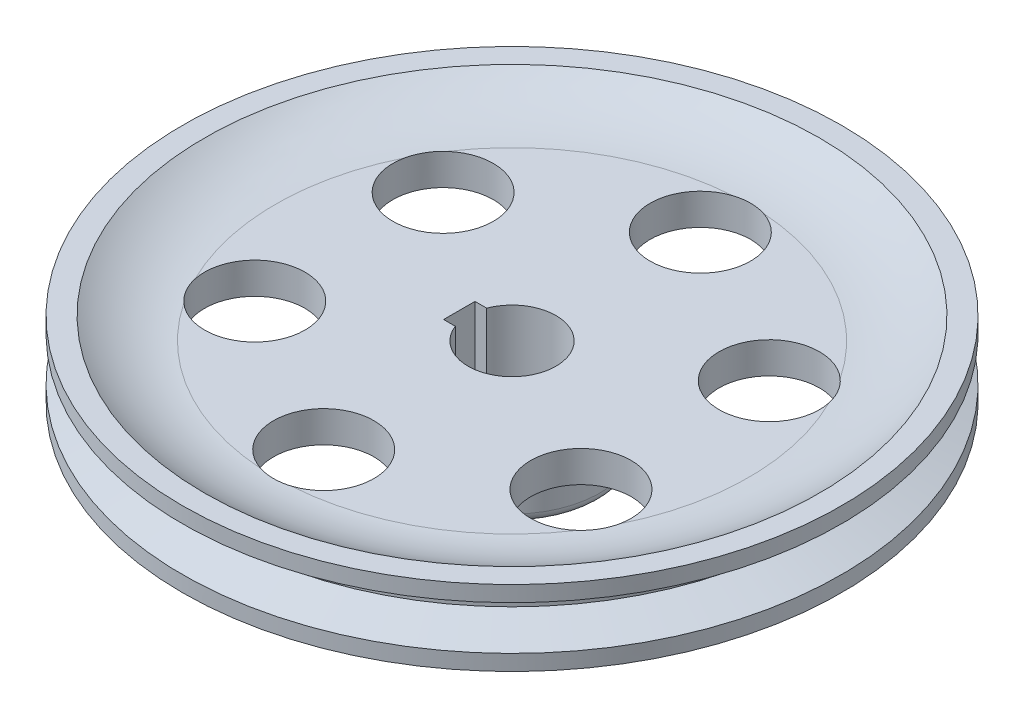
SolidWorks part; units mm, degrees
ref_plane "Front Plane" through (0, 0, 0) normal (0, 0, 1) x (1, 0, 0)
ref_plane "Top Plane" through (0, 0, 0) normal (0, 1, 0) x (1, 0, 0)
ref_plane "Right Plane" through (0, 0, 0) normal (1, 0, 0) x (0, 0, -1)
sketch "Sketch1" plane through (0, 0, 0) normal (0, 1, 0) x (1, 0, 0)
  circle A0 centre (0, 0) radius 52.5
  circle A1 centre (0, 0) radius 30 construction
  circle A2 centre (0, 30) radius 8
  circle A3 centre (25.9808, 15) radius 8
  circle A4 centre (25.9808, -15) radius 8
  circle A5 centre (0, -30) radius 8
  circle A6 centre (-25.9808, -15) radius 8
  circle A7 centre (-25.9808, 15) radius 8
  dimension "D1" = 105
  dimension "D2" = 60
  dimension "D3" = 16
  dimension "D4" = 6
extrude "Boss-Extrude1" add sketch "Sketch1" along normal mid plane 12
sketch "Sketch2" plane through (0, -6, 0) normal (0, -1, 0) x (1, 0, 0)
  circle A0 centre (0, 0) radius 14
  dimension "D1" = 28
extrude "Boss-Extrude2" add sketch "Sketch2" along normal blind 7
sketch "Sketch3" plane through (0, -13, 0) normal (0, -1, 0) x (1, 0, 0)
  line L0 (-67.4815, 0) -> (77.6813, 0) construction
  line L1 (0, 57.1338) -> (0, -59.499) construction
  line L2 (-8.4, 2.5) -> (-8.4, -2.5)
  line L3 (-8.4, 2.5) -> (-6.5383, 2.5)
  line L4 (-8.4, -2.5) -> (-6.5383, -2.5)
  arc A0 (-6.5383, -2.5) -> (-6.5383, 2.5) centre (0, 0) ccw
  point P9 (-8.4, 0)
  dimension "D1" = 14
  dimension "D2" = 8.4
  dimension "D3" = 5
extrude "Cut-Extrude1" cut sketch "Sketch3" against normal blind 77
sketch "Sketch4" plane through (0, 6, 0) normal (0, 1, 0) x (1, 0, 0)
  circle A0 centre (0, 0) radius 49
  dimension "D1" = 98
extrude "Cut-Extrude2" cut sketch "Sketch4" against normal blind 3.5 draft 40
fillet "Fillet1" radius 20 1 edges at (0, 2.5, 46.0632)
mirror "Mirror1" about plane through (0, 0, 0) normal (0, 1, 0) of "Cut-Extrude2"
sketch "Sketch5" plane through (0, 0, 0) normal (0, 0, 1) x (1, 0, 0)
  line L0 (178.7824, 0) -> (-73.7824, 0) construction
  line L1 (52.5, 3.5) -> (52.5, -3.5)
  line L2 (52.5, -6) -> (52.5, 6) construction
  line L3 (52.5, -3.5) -> (46.5, -1.3162)
  line L4 (46.5, -1.3162) -> (46.5, 1.3162)
  line L5 (46.5, 1.3162) -> (52.5, 3.5)
  line L6 (0, 0) -> (0, 30.3935) construction
  point P7 (46.5, 0)
  point P10 (52.5, 0)
  dimension "D1" = 7
  dimension "D2" = 40
  dimension "D3" = 46.5
revolve "Cut-Revolve1" cut sketch "Sketch5" angle 360 about L6
sketch "Sketch6" plane through (0, -13, 0) normal (0, -1, 0) x (1, 0, 0)
  line L0 (-8.4, 2.5) -> (-8.4, -2.5) construction
  line L1 (-8.4, 2.5) -> (-8.4, -2.5)
  line L2 (-8.4, -2.5) -> (-6.5383, -2.5) construction
  line L3 (-8.4, -2.5) -> (-6.5383, -2.5)
  line L4 (-6.5383, 2.5) -> (-8.4, 2.5) construction
  line L5 (-6.5383, 2.5) -> (-8.4, 2.5)
  arc A0 (-6.5383, -2.5) -> (-6.5383, 2.5) centre (0, 0) ccw construction
  circle A1 centre (0, 0) radius 14
  circle A2 centre (0, 0) radius 14
  arc A3 (-6.5383, -2.5) -> (-6.5383, 2.5) centre (0, 0) ccw
  dimension "D1" = 0
extrude "Boss-Extrude3" add sketch "Sketch6" against normal up to surface (10.5 mm away) up to face at (0, -2.5, -38)
fillet "Fillet2" radius 1.5 1 edges at (0, -13, -14)
fillet "Fillet3" radius 2 1 edges at (0, -2.5, -14)
